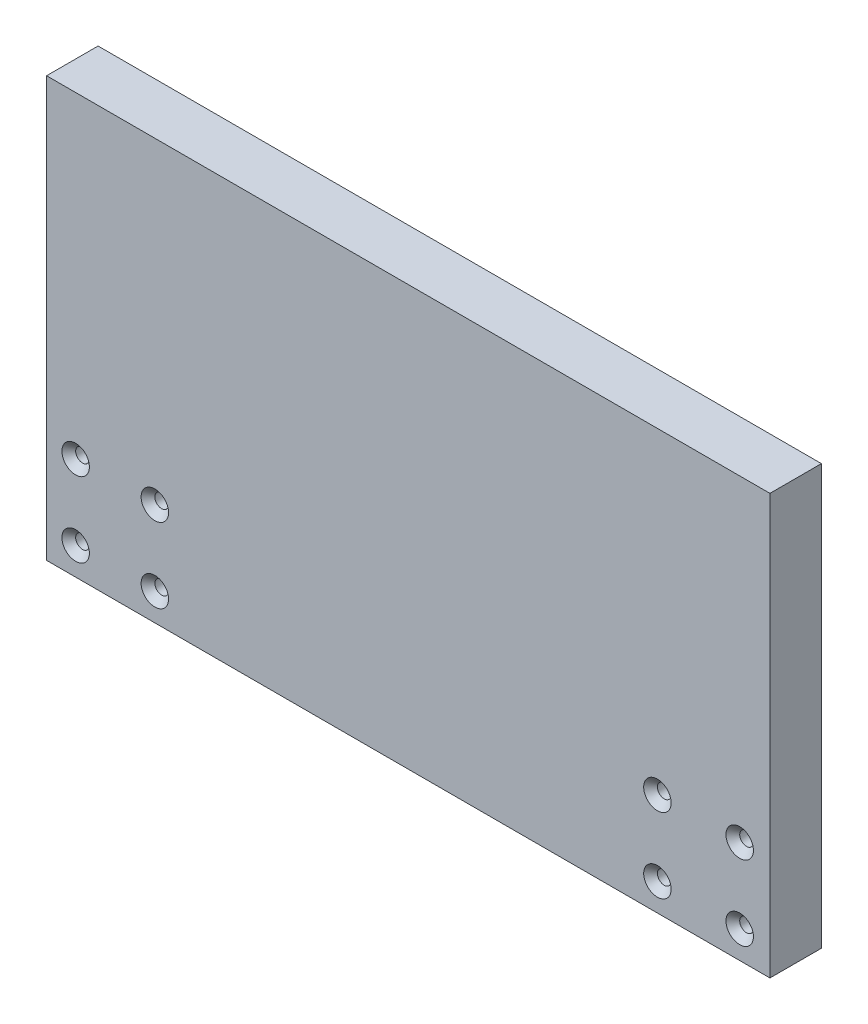
SolidWorks part; units mm, degrees
note: The reader was unsure of these and kept them because the rebuilt part matched: shared geometry of "Sketch2<3>".
material "McMaster 6061-T6"
ref_plane "Front" through (0, 0, 0) normal (0, 0, 1) x (1, 0, 0)
ref_plane "Top" through (0, 0, 0) normal (0, 1, 0) x (1, 0, 0)
ref_plane "Right" through (0, 0, 0) normal (1, 0, 0) x (0, 0, -1)
sketch "Sketch1" plane through (0, 0, 0) normal (0, 1, 0) x (1, 0, 0)
  line B0 (145.625, 87.9) -> (79.625, 87.9)
  line B1 (79.625, 87.9) -> (79.625, 25.4)
  line B2 (79.625, 25.4) -> (-125.375, 25.4)
  line B3 (-125.375, 25.4) -> (-125.375, 87.9)
  line B4 (-125.375, 87.9) -> (-145.625, 87.9)
  line B5 (-145.625, 87.9) -> (-145.625, 0)
  line B6 (-145.625, 0) -> (145.625, 0)
  line B7 (145.625, 0) -> (145.625, 87.9)
sketch_block_instance "Block-TopSection Base-1"
sketch_block "Block-TopSection Base" parameters "D1"=25.4
sketch "Sketch2" plane through (0, 0, 0) normal (0, 0, 1) x (1, 0, 0)
  line L0 (-145.625, 0) -> (-188.875, 0)
  line L1 (-188.875, 0) -> (-188.875, 60)
  line L2 (-188.875, 60) -> (-145.625, 60)
  line L3 (145.625, 60) -> (145.625, 194.1)
  line L4 (145.625, 194.1) -> (-188.875, 194.1)
  line L5 (-188.875, 194.1) -> (-188.875, 60)
  point P0 (-125.375, 0)
  line B0 (145.625, 0) -> (-145.625, 0)
  line B1 (145.625, 0) -> (145.625, 60)
  line B2 (145.625, 60) -> (-145.625, 60)
  line B3 (-145.625, 0) -> (-145.625, 60)
  arc B4 (101.925, 7) -> (95.325, 7) centre (98.625, 7) ccw
  arc B5 (95.325, 7) -> (101.925, 7) centre (98.625, 7) ccw
  arc B6 (82.325, 7) -> (88.925, 7) centre (85.625, 7) ccw
  arc B7 (88.925, 7) -> (82.325, 7) centre (85.625, 7) ccw
  arc B8 (82.325, 53) -> (88.925, 53) centre (85.625, 53) ccw
  arc B9 (88.925, 53) -> (82.325, 53) centre (85.625, 53) ccw
  arc B10 (95.325, 53) -> (101.925, 53) centre (98.625, 53) ccw
  arc B11 (101.925, 53) -> (95.325, 53) centre (98.625, 53) ccw
  circle B12 centre (139.275, 23.675) radius 1.5875
  circle B13 centre (113.875, 23.675) radius 1.5875
  circle B14 centre (113.875, 36.325) radius 1.5875
  circle B15 centre (139.275, 36.325) radius 1.5875
  arc B16 (-112.875, 31.75) -> (-112.875, 28.25) centre (-112.875, 30) ccw
  arc B17 (-112.875, 28.25) -> (-112.875, 31.75) centre (-112.875, 30) ccw
  arc B18 (-52.875, 31.75) -> (-52.875, 28.25) centre (-52.875, 30) ccw
  arc B19 (-52.875, 28.25) -> (-52.875, 31.75) centre (-52.875, 30) ccw
  arc B20 (7.125, 31.75) -> (7.125, 28.25) centre (7.125, 30) ccw
  arc B21 (7.125, 28.25) -> (7.125, 31.75) centre (7.125, 30) ccw
  arc B22 (67.125, 31.75) -> (67.125, 28.25) centre (67.125, 30) ccw
  arc B23 (67.125, 28.25) -> (67.125, 31.75) centre (67.125, 30) ccw
  arc B24 (-138.925, 7) -> (-132.325, 7) centre (-135.625, 7) ccw
  arc B25 (-132.325, 7) -> (-138.925, 7) centre (-135.625, 7) ccw
  arc B26 (-138.925, 53) -> (-132.325, 53) centre (-135.625, 53) ccw
  arc B27 (-132.325, 53) -> (-138.925, 53) centre (-135.625, 53) ccw
  dimension "D1" = 63.5
  dimension "D2" = 194.1
sketch_block_instance "Block-RightSection Side-1"
sketch_block "Block-RightSection Side"
extrude "Primary Extrusion" add sketch "Sketch2" against normal up to vertex (25.4 mm away) contours B3 B0 B1 B2 B27 B26 B25 B24 B23 B22 B21 B20 B19 B18 B17 B16 B15 B14 B13 B12 B11 B10 B9 B8 B7 B6 B5 B4 | B26 B27 | B24 B25 | B6 B7 | B4 B5 | B13 | B12 | B14 | B15 | B8 B9 | B10 B11 | B22 B23 | B18 B19 | B20 B21 | B16 B17 | L0 B3 L2 L1 | B2 L3 L4 L5 L2 up to point (-125.375, 0, -25.4)
extrude "Rail Mounting" cut sketch "Sketch2<3>" along normal blind 10 from surface at -25.4 contours B16 B17 | B18 B19 | B20 B21 | B22 B23 starting at face at (-21.625, 97.05, -25.4)
sketch "Sketch2<3>" plane through (0, 0, 0) normal (0, 0, 1) x (1, 0, 0) same geometry as "Sketch2"
sketch "Sketch3" plane through (0, 0, 0) normal (0, 0, 1) x (1, 0, 0)
  line L0 (-145.625, 0) -> (145.625, 0) construction
  line L1 (-188.875, 60) -> (-125.375, 60) construction
  line L2 (-188.875, 60) -> (-188.875, 0) construction
  line L3 (-188.875, 0) -> (-125.375, 0) construction
  line L4 (-125.375, 60) -> (-125.375, 0) construction
  line L5 (-138.8158, 60) -> (-138.8158, 0) construction
  line L6 (145.625, 60) -> (79.625, 60) construction
  line L7 (145.625, 60) -> (145.625, 0) construction
  line L8 (145.625, 0) -> (79.625, 0) construction
  line L9 (79.625, 60) -> (79.625, 0) construction
  line L10 (-138.8158, 47.3) -> (145.625, 47.3) construction
  line L11 (79.625, 60) -> (145.625, 0) construction
  line L12 (145.625, 60) -> (79.625, 0) construction
  line L13 (-125.375, 60) -> (-188.875, 0) construction
  line L15 (-125.375, 0) -> (-188.875, 60) construction
  line L17 (145.625, 60) -> (-145.625, 60) construction
  circle A0 centre (-138.8158, 47.3) radius 3.175
  circle A1 centre (-138.8158, 12.7) radius 3.175
  circle A2 centre (93.595, 47.3) radius 3.175
  circle A3 centre (131.655, 47.3) radius 3.175
  circle A4 centre (131.655, 12.7) radius 3.175
  circle A5 centre (93.595, 12.7) radius 3.175
  circle A6 centre (-175.4342, 12.7) radius 3.175
  circle A7 centre (-175.4342, 47.3) radius 3.175
  point P20 (93.595, 47.3)
  point P22 (131.655, 47.3)
  point P35 (-188.875, 60)
  point P36 (145.625, 60)
  point P37 (0, 0)
  point P38 (-138.8158, 60)
  point P40 (0, 0)
  point P41 (0, 0)
  dimension "D1" = 6.35
  dimension "D2" = 12.7
  dimension "D3" = 12.7
extrude "Cut-Extrude2" cut sketch "Sketch3" against normal through all
chamfer "Chamfer1" distance 3.175 angle 45 8 edges at (96.77, 47.3, 0) (134.83, 47.3, 0) (134.83, 12.7, 0) (96.77, 12.7, 0) (-135.6408, 12.7, 0) (-135.6408, 47.3, 0) (-172.2592, 47.3, 0) (-172.2592, 12.7, 0)
chamfer "Chamfer2" distance 1.5875 angle 45 4 edges at (-188.875, 97.05, -25.4) (-21.625, 0, -25.4) (145.625, 97.05, -25.4) (-21.625, 194.1, -25.4)
